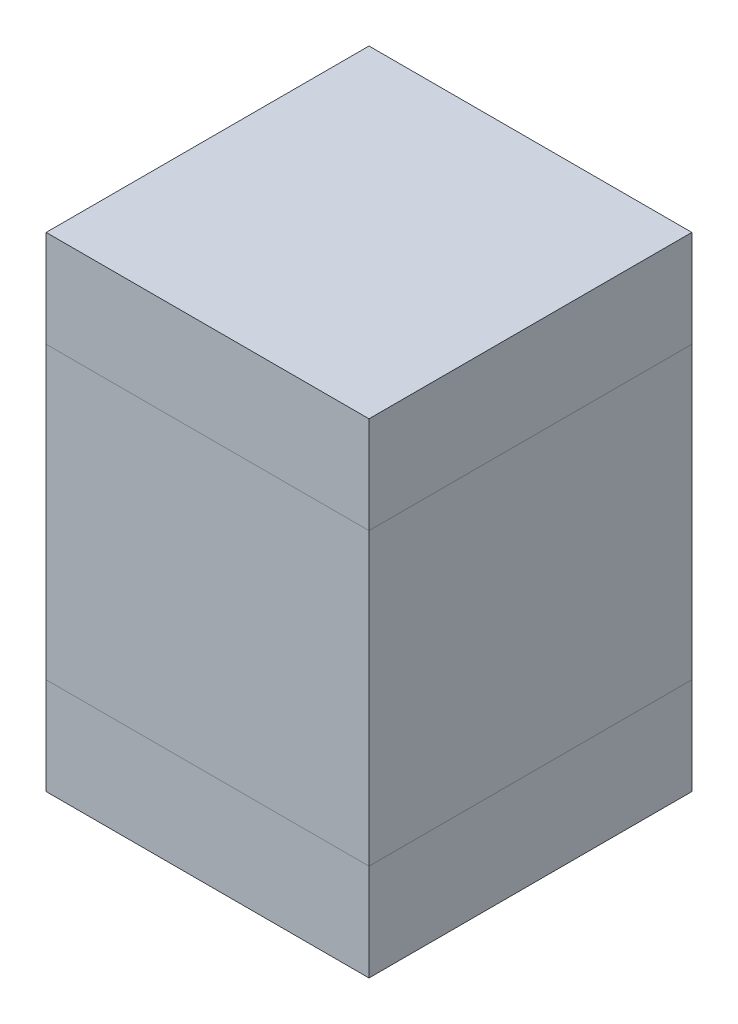
SolidWorks part; units mm, degrees
ref_plane "Front Plane" through (0, 0, 0) normal (0, 0, 1) x (1, 0, 0)
ref_plane "Top Plane" through (0, 0, 0) normal (0, 1, 0) x (1, 0, 0)
ref_plane "Right Plane" through (0, 0, 0) normal (1, 0, 0) x (0, 0, -1)
sketch "Sketch2" plane through (0, 0, 0) normal (0, 1, 0) x (1, 0, 0)
  line L1 (-25, -25) -> (25, -25)
  line L2 (-25, -25) -> (-25, 25)
  line L3 (-25, 25) -> (25, 25)
  line L4 (25, -25) -> (25, 25)
  line L5 (-25, -25) -> (25, 25) construction
  line L6 (-25, 25) -> (25, -25) construction
  point P0 (0, 0)
  dimension "D1" = 50
extrude "Boss-Extrude1" add sketch "Sketch2" along normal blind 15
extrude "Boss-Extrude2" add sketch "Sketch2<2>" along normal blind 45 from offset 15 separate body
sketch "Sketch2<2>" plane through (0, 0, 0) normal (0, 1, 0) x (1, 0, 0) same geometry as "Sketch2"
extrude "Boss-Extrude3" add sketch "Sketch2<3>" along normal blind 15 from offset 60 separate body
sketch "Sketch2<3>" plane through (0, 0, 0) normal (0, 1, 0) x (1, 0, 0) same geometry as "Sketch2"
